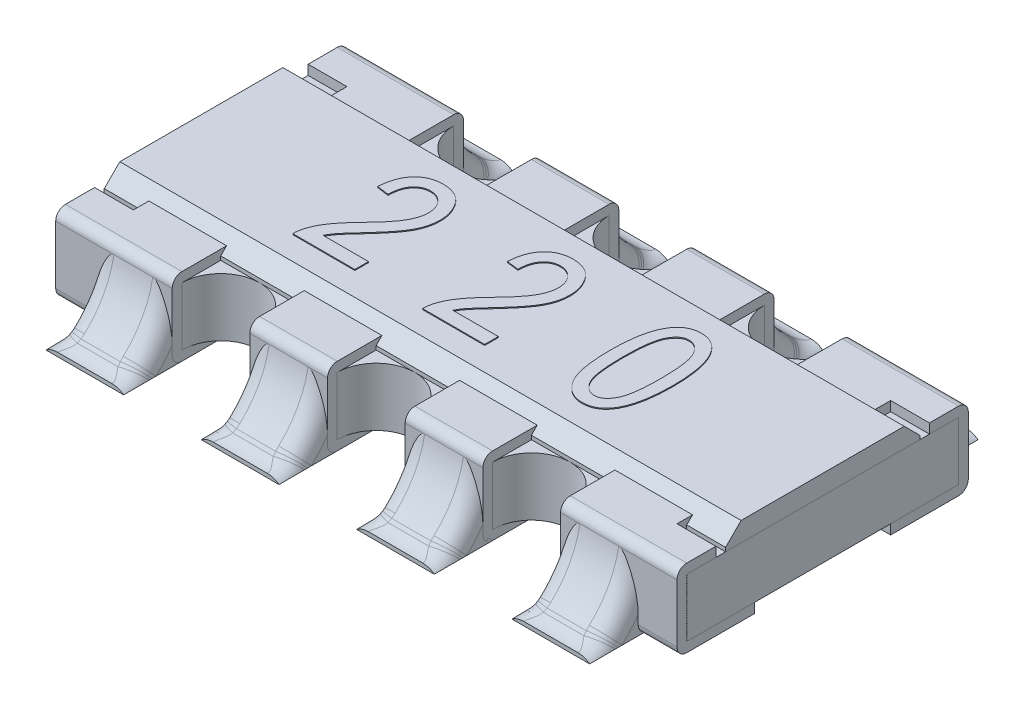
SolidWorks part; units mm, degrees
material "E-Glass Fiber"
ref_plane "Front Plane" through (0, 0, 0) normal (0, 0, 1) x (1, 0, 0)
ref_plane "Top Plane" through (0, 0, 0) normal (0, 1, 0) x (1, 0, 0)
ref_plane "Right Plane" through (0, 0, 0) normal (1, 0, 0) x (0, 0, -1)
sketch "Sketch5" plane through (0, 0, 0) normal (1, 0, 0) x (0, 0, -1)
  line L0 (55, 0) -> (-55, 0) construction
  line L1 (-0.7, 0.4) -> (0.7, 0.4)
  line L2 (-0.75, 0.35) -> (-0.75, 0.05)
  line L3 (-0.7, 0) -> (-0.35, 0)
  line L4 (0.75, 0.35) -> (0.75, 0.05)
  line L5 (0, 55) -> (0, -55) construction
  line L8 (0.35, 0) -> (0.7, 0)
  arc A0 (0.7, 0.4) -> (0.75, 0.35) centre (0.7, 0.35) cw
  arc A1 (0.7, 0) -> (0.75, 0.05) centre (0.7, 0.05) ccw
  arc A2 (-0.75, 0.05) -> (-0.7, 0) centre (-0.7, 0.05) ccw
  arc A3 (-0.7, 0.4) -> (-0.75, 0.35) centre (-0.7, 0.35) ccw
  point P10 (0.75, 0.4)
  point P13 (0.75, 0)
  point P18 (-0.75, 0.4)
  dimension "D4" = 0.05
  dimension "D1" = 0.4
  dimension "D2" = 1.5
  dimension "D3" = 0.75
  dimension "D5" = 0.4
  dimension "D6" = 0.4
extrude "Extrude-Thin1" add sketch "Sketch5" along normal mid plane 3.2 thin thin type one direction reverse wall 0.05
sketch "Sketch6" plane through (0, 0.4, 0) normal (0, 1, 0) x (1, 0, 0)
  line L1 (1.6, 0.75) -> (-1.6, 0.75) construction
  line L2 (-1, 0.75) -> (-0.6, 0.75)
  line L3 (-1, 0.75) -> (-1, 0.25)
  line L4 (-1, 0.25) -> (-0.6, 0.25)
  line L6 (-0.6, 0.75) -> (-0.6, 0.25)
  line L7 (0, -0.22) -> (0, 0.22) construction
  line L8 (-0.2, 0.75) -> (0.2, 0.75)
  line L9 (-0.2, 0.75) -> (-0.2, 0.25)
  line L10 (-0.2, 0.25) -> (0.2, 0.25)
  line L11 (0.2, 0.75) -> (0.2, 0.25)
  line L12 (0.6, 0.75) -> (1, 0.75)
  line L13 (0.6, 0.75) -> (0.6, 0.25)
  line L14 (0.6, 0.25) -> (1, 0.25)
  line L15 (1, 0.75) -> (1, 0.25)
  line L16 (1.6, 0.7) -> (1.6, -0.7) construction
  line L18 (1.6, -0.75) -> (-1.6, -0.75) construction
  line L19 (-1, -0.75) -> (-0.6, -0.75)
  line L20 (-1, -0.75) -> (-1, -0.25)
  line L21 (-1, -0.25) -> (-0.6, -0.25)
  line L22 (-0.6, -0.75) -> (-0.6, -0.25)
  line L24 (-0.2, -0.75) -> (0.2, -0.75)
  line L25 (-0.2, -0.75) -> (-0.2, -0.25)
  line L26 (-0.2, -0.25) -> (0.2, -0.25)
  line L27 (0.2, -0.75) -> (0.2, -0.25)
  line L28 (0.6, -0.75) -> (1, -0.75)
  line L29 (0.6, -0.75) -> (0.6, -0.25)
  line L30 (0.6, -0.25) -> (1, -0.25)
  line L31 (1, -0.75) -> (1, -0.25)
  dimension "D1" = 0.5
  dimension "D2" = 0.4
  dimension "D3" = 0.8
  dimension "D4" = 0.2
  dimension "D5" = 0.8
  dimension "D6" = 0.4
  dimension "D7" = 0.4
  dimension "D8" = 0.6
extrude "Cut-Extrude3" cut sketch "Sketch6" against normal through all
sketch "Sketch7" plane through (0, 0.4, 0) normal (0, 1, 0) x (1, 0, 0)
  line L0 (-1.6, 0.7) -> (-1.6, -0.7) construction
  line L1 (-1.6, -0.55) -> (-1.4, -0.55)
  line L2 (-1.6, -0.55) -> (-1.6, 0.55)
  line L3 (-1.6, 0.55) -> (-1.4, 0.55)
  line L4 (-1.4, -0.55) -> (-1.4, 0.55)
  line L5 (1.6, 0.7) -> (1.6, -0.7) construction
  line L6 (1.6, -0.55) -> (1.4, -0.55)
  line L7 (1.6, -0.55) -> (1.6, 0.55)
  line L8 (1.6, 0.55) -> (1.4, 0.55)
  line L9 (1.4, -0.55) -> (1.4, 0.55)
  line L12 (-0.22, 0) -> (0.22, 0) construction
  dimension "D1" = 0.55
  dimension "D2" = 1.1
  dimension "D3" = 0.2
extrude "Cut-Extrude4" cut sketch "Sketch7" against normal blind 0.1
sketch "Sketch1" plane through (0, 0.05, 0) normal (0, 1, 0) x (1, 0, 0)
  line L0 (-1.6, -0.7) -> (1.6, 0.7) construction
  line L1 (-1.6, 0.7) -> (1.6, 0.7)
  line L2 (-1.6, 0.7) -> (-1.6, -0.7)
  line L3 (-1.6, -0.7) -> (1.6, -0.7)
  line L4 (1.6, 0.7) -> (1.6, -0.7)
  line L5 (-1.2, 0.7) -> (-1.2, -0.7) construction
  line L6 (-1.6, 0.5) -> (1.6, 0.5) construction
  line L7 (-0.4, 0.7) -> (-0.4, -0.7) construction
  line L8 (-1.6, -0.5) -> (1.6, -0.5) construction
  line L9 (0.4, 0.7) -> (0.4, -0.7) construction
  line L10 (0, -0.22) -> (0, 0.22) construction
  line L11 (1.2, 0.7) -> (1.2, -0.7) construction
  dimension "D3" = 0.2
  dimension "D1" = 3.2
  dimension "D2" = 1.4
  dimension "D4" = 0.2
  dimension "D5" = 0.8
  dimension "D6" = 0.8
  dimension "D7" = 0.8
  dimension "D8" = 0.4
extrude "Boss-Extrude3" add sketch "Sketch1" along normal blind 0.3 separate body
sketch "Sketch9" plane through (0, 0.35, 0) normal (0, 1, 0) x (1, 0, 0)
  line L1 (-1.6, 0.5) -> (1.6, 0.5)
  line L2 (-1.6, 0.5) -> (-1.6, -0.5)
  line L3 (-1.6, -0.5) -> (1.6, -0.5)
  line L4 (1.6, 0.5) -> (1.6, -0.5)
extrude "Boss-Extrude4" add sketch "Sketch9" along normal blind 0.1
chamfer "Chamfer1" distance 0.08 angle 45 2 edges at (0, 0.45, 0.5) (0, 0.45, -0.5)
sketch "Sketch10" plane through (0, 0.05, 0) normal (0, 1, 0) x (1, 0, 0)
  line L0 (-1.6, 0.7) -> (1.6, 0.7) construction
  line L1 (-1.6, -0.7) -> (1.6, -0.7) construction
  line L2 (0, -0.22) -> (0, 0.22) construction
  circle A0 centre (-0.8, 0.7) radius 0.2
  circle A1 centre (0, 0.7) radius 0.2
  circle A2 centre (0.8, 0.7) radius 0.2
  circle A3 centre (0.8, -0.7) radius 0.2
  circle A4 centre (0, -0.7) radius 0.2
  circle A5 centre (-0.8, -0.7) radius 0.2
  dimension "D3" = 0.4
  dimension "D1" = 0.8
  dimension "D2" = 0.8
extrude "Cut-Extrude7" cut sketch "Sketch10" along normal blind 5
sketch "Sketch11" plane through (0, 0.45, 0) normal (0, 1, 0) x (1, 0, 0)
  line L0 (0, -0.22) -> (0, 0.22) construction
  line L2 (-0.22, 0) -> (0.22, 0) construction
  text T0 "2 2 0\r\n" font "Arial Narrow" height 0.6
  dimension "D1" = 0.86
  dimension "D2" = 0.3
extrude "Boss-Extrude5" add sketch "Sketch11" along normal blind 0.005
ref_plane "Plane1" through (-1.2, 0, 0) normal (1, 0, 0) x (0, 0, -1)
sketch "Sketch12" plane through (-1.2, 0, 0) normal (1, 0, 0) x (0, 0, -1)
  line L0 (-0.75, 0.35) -> (-0.75, 0.05)
  line L1 (-0.75, 0.05) -> (-0.7, 0)
  line L2 (0.825, 0) -> (-0.825, 0) construction
  line L3 (-0.7, 0) -> (-1, 0)
  line L4 (-1, 0) -> (-1, 0.02)
  line L5 (0, 0.22) -> (0, -0.22) construction
  line L6 (0.75, 0.05) -> (0.7, 0)
  line L7 (0.7, 0) -> (1, 0)
  line L8 (1, 0) -> (1, 0.02)
  line L9 (0.75, 0.35) -> (0.75, 0.05)
  arc A0 (-0.75, 0.05) -> (-0.7, 0) centre (-0.7, 0.05) ccw construction
  arc A1 (-1, 0.02) -> (-0.9338, 0.045) centre (-1, 0.12) ccw
  arc A2 (-0.9338, 0.045) -> (-0.9186, 0.0582) centre (-0.272, -0.7047) cw
  arc A3 (-0.9186, 0.0582) -> (-0.75, 0.35) centre (-1.2419, 0.4396) ccw
  arc A4 (1, 0.02) -> (0.9338, 0.045) centre (1, 0.12) cw
  arc A5 (0.9338, 0.045) -> (0.9186, 0.0582) centre (0.272, -0.7047) ccw
  arc A6 (0.9186, 0.0582) -> (0.75, 0.35) centre (1.2419, 0.4396) cw
  dimension "D2" = 0.5
  dimension "D3" = 0.1
  dimension "D4" = 1
  dimension "D1" = 0.02
  dimension "D5" = 1
  dimension "D6" = 0.7047
  dimension "D7" = 1
extrude "Boss-Extrude6" add sketch "Sketch12" along normal mid plane 0.4 separate body
fillet "Fillet1" radius 0.1 6 edges at (-1.4, 0.1895, 0.809) (-1.4, 0.0265, 0.9646) (-1, 0.1895, 0.809) (-1, 0.0265, 0.9646) (-1.4, 0.0516, 0.9263) (-1, 0.0516, 0.9263)
fillet "Fillet2" radius 0.1 6 edges at (-1, 0.0265, -0.9646) (-1, 0.1895, -0.809) (-1.4, 0.0265, -0.9646) (-1.4, 0.1895, -0.809) (-1, 0.0516, -0.9263) (-1.4, 0.0516, -0.9263)
pattern_linear "LPattern3" count 4 spacing 0.8 along (1, 0, 0) of bodies 114 113
